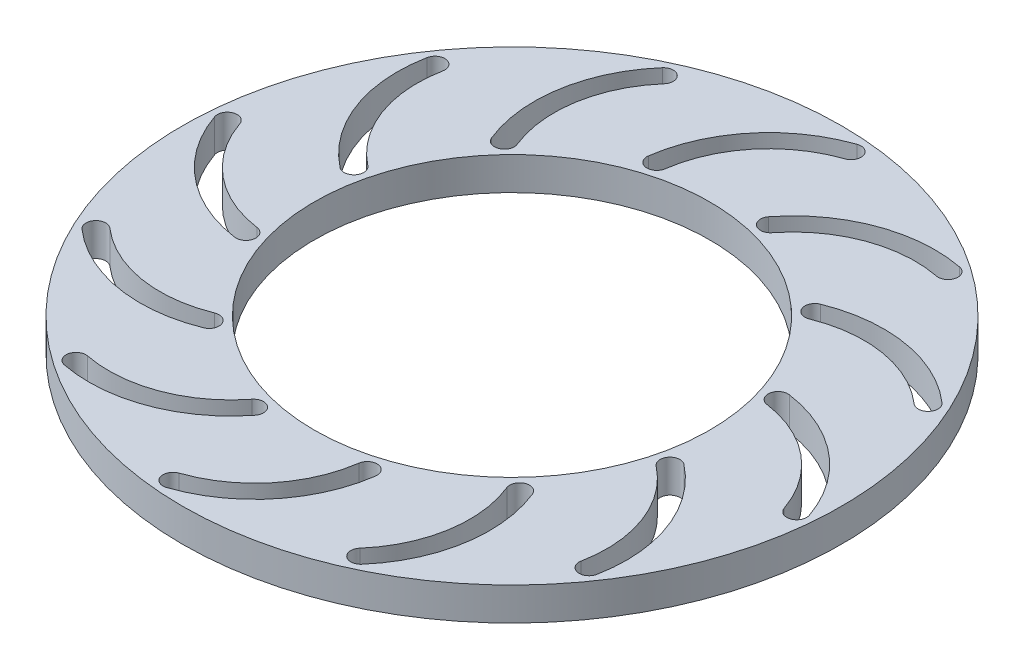
SolidWorks part; units mm, degrees
ref_plane "Front Plane" through (0, 0, 0) normal (0, 0, 1) x (1, 0, 0)
ref_plane "Top Plane" through (0, 0, 0) normal (0, 1, 0) x (1, 0, 0)
ref_plane "Right Plane" through (0, 0, 0) normal (1, 0, 0) x (0, 0, -1)
sketch "Sketch1" plane through (0, 0, 0) normal (0, 1, 0) x (1, 0, 0)
  circle A0 centre (0, 0) radius 3
  circle A1 centre (0, 0) radius 5
  circle A2 centre (0, 0) radius 3.25
  circle A3 centre (0, 0) radius 4.75
  arc A4 (0.7617, 3.1595) -> (2.7232, 3.8919) centre (2.3385, 1.9292) cw construction
  arc A5 (2.752, 4.0391) -> (0.6434, 3.2518) centre (2.3385, 1.9292) ccw
  arc A6 (2.6943, 3.7447) -> (0.8799, 3.0672) centre (2.3385, 1.9292) ccw
  arc A7 (2.6943, 3.7447) -> (2.752, 4.0391) centre (2.7232, 3.8919) ccw
  arc A8 (0.6434, 3.2518) -> (0.8799, 3.0672) centre (0.7617, 3.1595) ccw
  arc A9 (4.2057, 1.8958) -> (2.2956, 2.2163) centre (2.9898, 0.5015) ccw
  arc A10 (4.2057, 1.8958) -> (4.4029, 2.1219) centre (4.3043, 2.0089) ccw
  arc A11 (2.1831, 2.4944) -> (2.2956, 2.2163) centre (2.2394, 2.3554) ccw
  arc A12 (4.4029, 2.1219) -> (2.1831, 2.4944) centre (2.9898, 0.5015) ccw
  arc A13 (2.2394, 2.3554) -> (4.3043, 2.0089) centre (2.9898, 0.5015) cw construction
  arc A14 (4.5902, -0.461) -> (3.0963, 0.7716) centre (2.84, -1.0606) ccw
  arc A15 (4.5902, -0.461) -> (4.874, -0.3638) centre (4.7321, -0.4124) ccw
  arc A16 (3.1378, 1.0687) -> (3.0963, 0.7716) centre (3.117, 0.9201) ccw
  arc A17 (4.874, -0.3638) -> (3.1378, 1.0687) centre (2.84, -1.0606) ccw
  arc A18 (3.117, 0.9201) -> (4.7321, -0.4124) centre (2.84, -1.0606) cw construction
  arc A19 (3.7447, -2.6943) -> (3.0672, -0.8799) centre (1.9292, -2.3385) ccw
  arc A20 (3.7447, -2.6943) -> (4.0391, -2.752) centre (3.8919, -2.7232) ccw
  arc A21 (3.2518, -0.6434) -> (3.0672, -0.8799) centre (3.1595, -0.7617) ccw
  arc A22 (4.0391, -2.752) -> (3.2518, -0.6434) centre (1.9292, -2.3385) ccw
  arc A23 (3.1595, -0.7617) -> (3.8919, -2.7232) centre (1.9292, -2.3385) cw construction
  arc A24 (1.8958, -4.2057) -> (2.2163, -2.2956) centre (0.5015, -2.9898) ccw
  arc A25 (1.8958, -4.2057) -> (2.1219, -4.4029) centre (2.0089, -4.3043) ccw
  arc A26 (2.4944, -2.1831) -> (2.2163, -2.2956) centre (2.3554, -2.2394) ccw
  arc A27 (2.1219, -4.4029) -> (2.4944, -2.1831) centre (0.5015, -2.9898) ccw
  arc A28 (2.3554, -2.2394) -> (2.0089, -4.3043) centre (0.5015, -2.9898) cw construction
  arc A29 (-0.461, -4.5902) -> (0.7716, -3.0963) centre (-1.0606, -2.84) ccw
  arc A30 (-0.461, -4.5902) -> (-0.3638, -4.874) centre (-0.4124, -4.7321) ccw
  arc A31 (1.0687, -3.1378) -> (0.7716, -3.0963) centre (0.9201, -3.117) ccw
  arc A32 (-0.3638, -4.874) -> (1.0687, -3.1378) centre (-1.0606, -2.84) ccw
  arc A33 (0.9201, -3.117) -> (-0.4124, -4.7321) centre (-1.0606, -2.84) cw construction
  arc A34 (-2.6943, -3.7447) -> (-0.8799, -3.0672) centre (-2.3385, -1.9292) ccw
  arc A35 (-2.6943, -3.7447) -> (-2.752, -4.0391) centre (-2.7232, -3.8919) ccw
  arc A36 (-0.6434, -3.2518) -> (-0.8799, -3.0672) centre (-0.7617, -3.1595) ccw
  arc A37 (-2.752, -4.0391) -> (-0.6434, -3.2518) centre (-2.3385, -1.9292) ccw
  arc A38 (-0.7617, -3.1595) -> (-2.7232, -3.8919) centre (-2.3385, -1.9292) cw construction
  arc A39 (-4.2057, -1.8958) -> (-2.2956, -2.2163) centre (-2.9898, -0.5015) ccw
  arc A40 (-4.2057, -1.8958) -> (-4.4029, -2.1219) centre (-4.3043, -2.0089) ccw
  arc A41 (-2.1831, -2.4944) -> (-2.2956, -2.2163) centre (-2.2394, -2.3554) ccw
  arc A42 (-4.4029, -2.1219) -> (-2.1831, -2.4944) centre (-2.9898, -0.5015) ccw
  arc A43 (-2.2394, -2.3554) -> (-4.3043, -2.0089) centre (-2.9898, -0.5015) cw construction
  arc A44 (-4.5902, 0.461) -> (-3.0963, -0.7716) centre (-2.84, 1.0606) ccw
  arc A45 (-4.5902, 0.461) -> (-4.874, 0.3638) centre (-4.7321, 0.4124) ccw
  arc A46 (-3.1378, -1.0687) -> (-3.0963, -0.7716) centre (-3.117, -0.9201) ccw
  arc A47 (-4.874, 0.3638) -> (-3.1378, -1.0687) centre (-2.84, 1.0606) ccw
  arc A48 (-3.117, -0.9201) -> (-4.7321, 0.4124) centre (-2.84, 1.0606) cw construction
  arc A49 (-3.7447, 2.6943) -> (-3.0672, 0.8799) centre (-1.9292, 2.3385) ccw
  arc A50 (-3.7447, 2.6943) -> (-4.0391, 2.752) centre (-3.8919, 2.7232) ccw
  arc A51 (-3.2518, 0.6434) -> (-3.0672, 0.8799) centre (-3.1595, 0.7617) ccw
  arc A52 (-4.0391, 2.752) -> (-3.2518, 0.6434) centre (-1.9292, 2.3385) ccw
  arc A53 (-3.1595, 0.7617) -> (-3.8919, 2.7232) centre (-1.9292, 2.3385) cw construction
  arc A54 (-1.8958, 4.2057) -> (-2.2163, 2.2956) centre (-0.5015, 2.9898) ccw
  arc A55 (-1.8958, 4.2057) -> (-2.1219, 4.4029) centre (-2.0089, 4.3043) ccw
  arc A56 (-2.4944, 2.1831) -> (-2.2163, 2.2956) centre (-2.3554, 2.2394) ccw
  arc A57 (-2.1219, 4.4029) -> (-2.4944, 2.1831) centre (-0.5015, 2.9898) ccw
  arc A58 (-2.3554, 2.2394) -> (-2.0089, 4.3043) centre (-0.5015, 2.9898) cw construction
  arc A59 (0.461, 4.5902) -> (-0.7716, 3.0963) centre (1.0606, 2.84) ccw
  arc A60 (0.461, 4.5902) -> (0.3638, 4.874) centre (0.4124, 4.7321) ccw
  arc A61 (-1.0687, 3.1378) -> (-0.7716, 3.0963) centre (-0.9201, 3.117) ccw
  arc A62 (0.3638, 4.874) -> (-1.0687, 3.1378) centre (1.0606, 2.84) ccw
  arc A63 (-0.9201, 3.117) -> (0.4124, 4.7321) centre (1.0606, 2.84) cw construction
  point P6 (1.6389, 3.8029)
  point P14 (3.3208, 2.4739)
  point P15 (0, 0)
  point P24 (4.1129, 0.4821)
  point P32 (3.8029, -1.6389)
  point P40 (2.4739, -3.3208)
  point P48 (0.4821, -4.1129)
  point P56 (-1.6389, -3.8029)
  point P64 (-3.3208, -2.4739)
  point P72 (-4.1129, -0.4821)
  point P80 (-3.8029, 1.6389)
  point P88 (-2.4739, 3.3208)
  point P96 (-0.4821, 4.1129)
  point P104 (0, 0)
  dimension "D1" = 6
  dimension "D2" = 0.25
  dimension "1" = 10
  dimension "D3" = 0.25
  dimension "D4" = 2
  dimension "D6" = 12
extrude "Boss-Extrude1" add sketch "Sketch1" along normal blind 0.5 contours A1 | A0
extrude "Cut-Extrude2" cut sketch "Sketch1<4>" along normal blind 0.5 contours A49 A51 A52 A50
sketch "Sketch1<4>" plane through (0, 0, 0) normal (0, 1, 0) x (1, 0, 0) same geometry as "Sketch1"
extrude "Cut-Extrude3" cut sketch "Sketch1<6>" along normal blind 0.5 contours A54 A56 A57 A55 | A59 A61 A62 A60 | A6 A8 A5 A7
sketch "Sketch1<6>" plane through (0, 0, 0) normal (0, 1, 0) x (1, 0, 0) same geometry as "Sketch1"
extrude "Cut-Extrude5" cut sketch "Sketch1<7>" along normal blind 0.5 contours A12 A11 A9 A10 | A17 A16 A14 A15 | A22 A21 A19 A20 | A27 A26 A24 A25 | A32 A31 A29 A30 | A34 A36 A37 A35 | A39 A41 A42 A40 | A44 A46 A47 A45
sketch "Sketch1<7>" plane through (0, 0, 0) normal (0, 1, 0) x (1, 0, 0) same geometry as "Sketch1"
